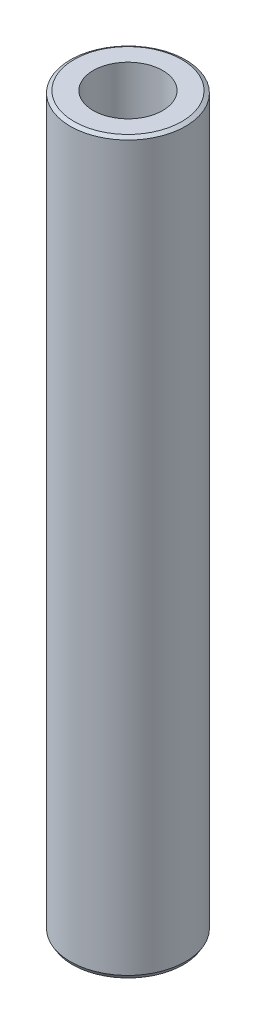
SolidWorks part; units mm, degrees
ref_plane "Front Plane" through (0, 0, 0) normal (0, 0, 1) x (1, 0, 0)
ref_plane "Top Plane" through (0, 0, 0) normal (0, 1, 0) x (1, 0, 0)
ref_plane "Right Plane" through (0, 0, 0) normal (1, 0, 0) x (0, 0, -1)
sketch "Sketch1" plane through (0, 0, 0) normal (0, 1, 0) x (1, 0, 0)
  circle A0 centre (0, 0) radius 27.5
  dimension "SHAFT_OD" = 55
extrude "Boss-Extrude1" add sketch "Sketch1" along normal blind 348.1032
sketch "Sketch2" plane through (0, 0, 0) normal (0, 1, 0) x (1, 0, 0)
  circle A0 centre (0, 0) radius 16.5801
  dimension "BORE_D" = 33.1602
extrude "Cut-Extrude1" cut sketch "Sketch2" along normal through all
chamfer "Chamfer1" distance 1.0446 angle 60 2 edges at (0, 348.1032, 27.5) (0, 0, 27.5) first distance on face at (0, 348.1032, 27.5) first distance on face at (0, 0, 16.5801)
